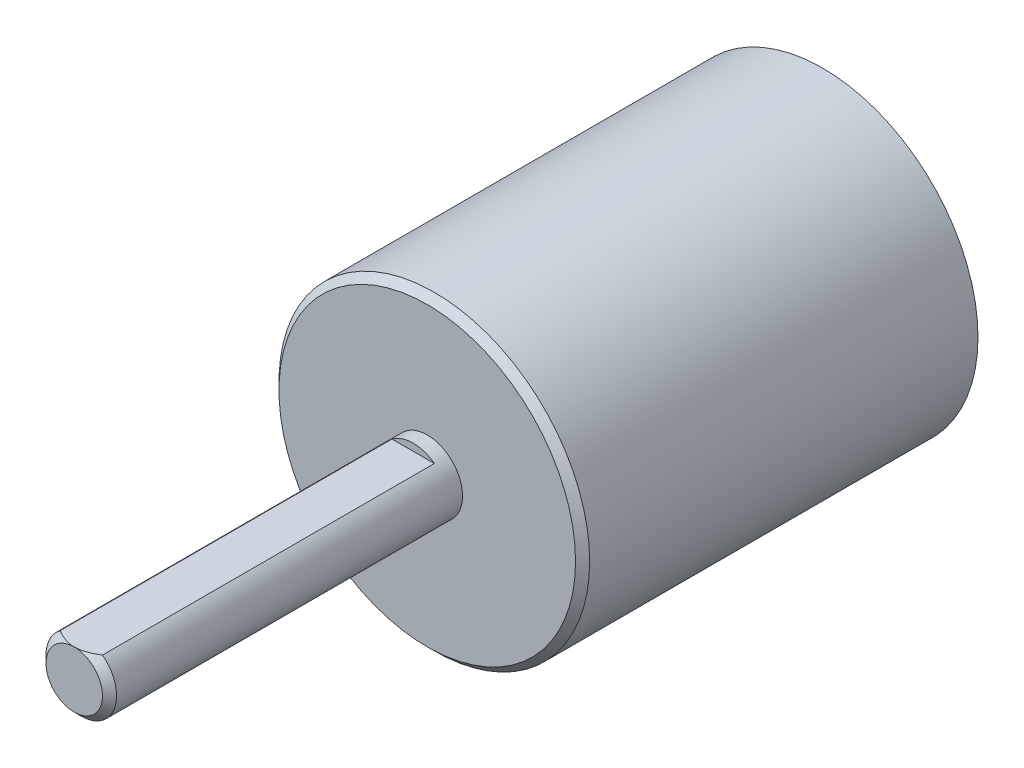
SolidWorks part; units mm, degrees
ref_plane "Front Plane" through (0, 0, 0) normal (0, 0, 1) x (1, 0, 0)
ref_plane "Top Plane" through (0, 0, 0) normal (0, 1, 0) x (1, 0, 0)
ref_plane "Right Plane" through (0, 0, 0) normal (1, 0, 0) x (0, 0, -1)
sketch "Sketch1" plane through (0, 0, 0) normal (0, 0, 1) x (1, 0, 0)
  line L0 (-1.5, 2) -> (1.5, 2)
  circle A0 centre (0, 0) radius 11
  circle A1 centre (0, 0) radius 2.5
  dimension "D1" = 22
  dimension "D2" = 5
  dimension "D3" = 2
extrude "Boss-Extrude1" add sketch "Sketch1" along normal blind 28 contours A0 A1 | L0 A1 | L0 A1 region at (0, 2.2018, 0) region at (0, -0.1209, 0) region at (-10.6889, 0, 0)
extrude "Boss-Extrude2" add sketch "Sketch1<3>" along normal blind 25 from surface contours L0 A1 | L0 A1 region at (0, 2.2018, 0) region at (0, -0.1209, 0) starting at face at (11, 0, 28)
sketch "Sketch1<3>" plane through (0, 0, 0) normal (0, 0, 1) x (1, 0, 0) same geometry as "Sketch1"
extrude "Cut-Extrude1" cut sketch "Sketch1<4>" against normal blind 24 from surface contours L0 A1 region at (0, 2.2018, 0) starting at face at (2.5, 0, 53)
sketch "Sketch1<4>" plane through (0, 0, 0) normal (0, 0, 1) x (1, 0, 0) same geometry as "Sketch1"
chamfer "Chamfer1" distance 0.5 angle 45 2 edges at (11, 0, 28) (0, -2.5, 53)
